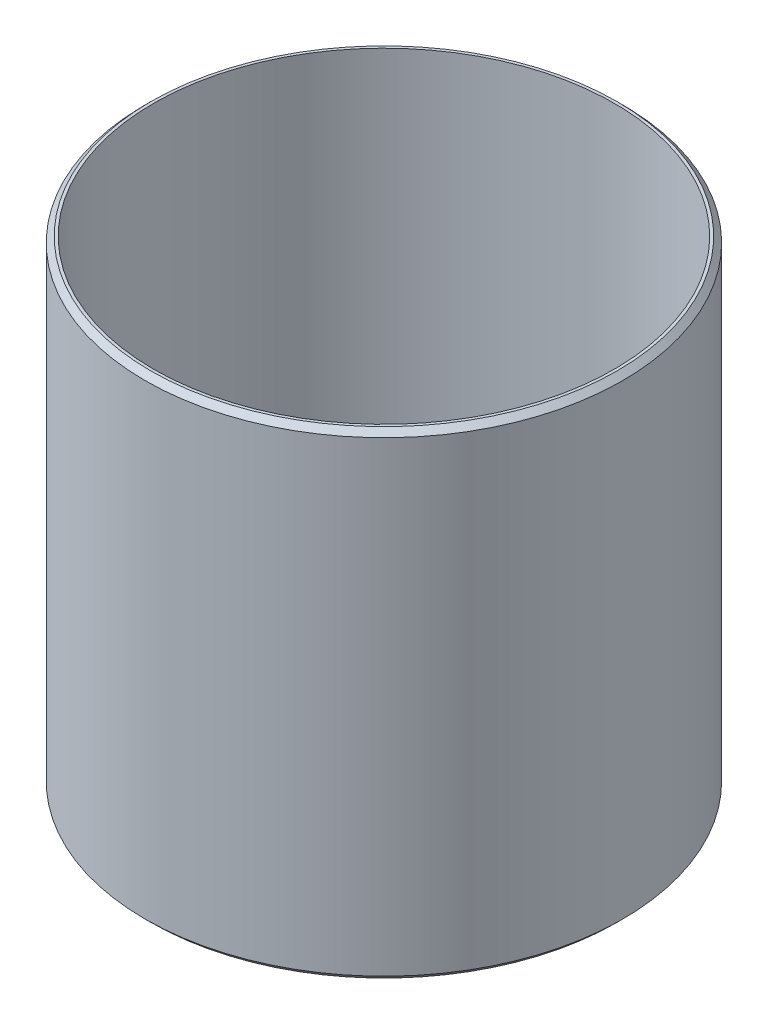
SolidWorks part; units mm, degrees
ref_plane "Front Plane" through (0, 0, 0) normal (0, 0, 1) x (1, 0, 0)
ref_plane "Top Plane" through (0, 0, 0) normal (0, 1, 0) x (1, 0, 0)
ref_plane "Right Plane" through (0, 0, 0) normal (1, 0, 0) x (0, 0, -1)
sketch "Sketch1" plane through (0, 0, 0) normal (0, 1, 0) x (1, 0, 0)
  circle A0 centre (0, 0) radius 81.9998
  circle A1 centre (0, 0) radius 84.9998
  point P5 (0, 0)
  dimension "D1" = 169.9997
  dimension "D2" = 3
extrude "Boss-Extrude1" add sketch "Sketch1" along normal blind 170
chamfer "Chamfer1" distance 2 angle 45 2 edges at (0, 0, 84.9998) (0, 170, 84.9998)
